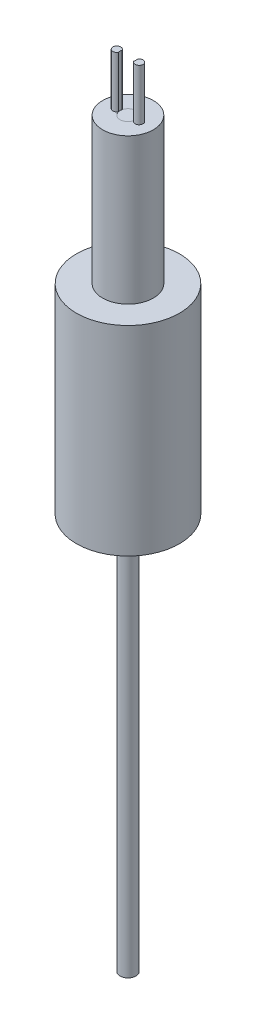
SolidWorks part; units mm, degrees
ref_plane "前视基准面" through (0, 0, 0) normal (0, 0, 1) x (1, 0, 0)
ref_plane "上视基准面" through (0, 0, 0) normal (0, 1, 0) x (1, 0, 0)
ref_plane "右视基准面" through (0, 0, 0) normal (1, 0, 0) x (0, 0, -1)
other "Configuration Table"
sketch "Sketch1" plane through (0, 0, 0) normal (0, 1, 0) x (1, 0, 0)
  circle A0 centre (0, 0) radius 3.2
  circle A1 centre (0, 0) radius 6.5
  circle A2 centre (1.4059, 0) radius 0.5
  circle A4 centre (-1.4059, 0) radius 0.5
  circle A5 centre (0, 0) radius 1
extrude "Boss-Extrude1" add sketch "Sketch1" along normal blind 50.1 contours A2 | A4 region at (1.4244, 0, 0) region at (-1.4244, 0, 0)
extrude "Boss-Extrude2" add sketch "Sketch1<3>" along normal blind 43.6 contours A0 A4 A2 region at (-3.1095, 0, 0)
sketch "Sketch1<3>" plane through (0, 0, 0) normal (0, 1, 0) x (1, 0, 0) same geometry as "Sketch1"
extrude "Boss-Extrude3" add sketch "Sketch1<4>" along normal blind 25.2 contours A1 A0 region at (-6.3162, 0, 0)
sketch "Sketch1<4>" plane through (0, 0, 0) normal (0, 1, 0) x (1, 0, 0) same geometry as "Sketch1"
extrude "Boss-Extrude4" add sketch "Sketch1<5>" against normal blind 50 and the other way blind 43.6 separate body contours A2 A5 A4 | A4 A5 | A2 A5 region at (0.9561, 0, 0) region at (0, 0, 0) region at (-0.9561, 0, 0)
sketch "Sketch1<5>" plane through (0, 0, 0) normal (0, 1, 0) x (1, 0, 0) same geometry as "Sketch1"
